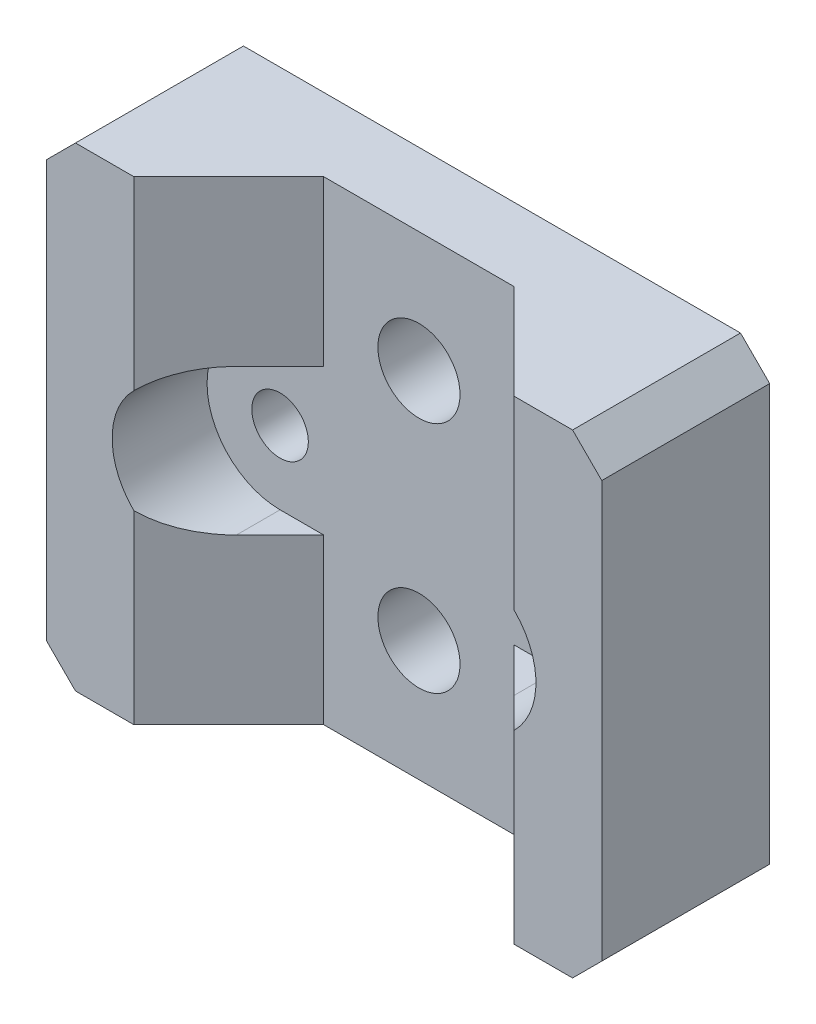
SolidWorks part; units mm, degrees
material "PET"
ref_plane "Front Plane" through (0, 0, 0) normal (0, 0, 1) x (1, 0, 0)
ref_plane "Top Plane" through (0, 0, 0) normal (0, 1, 0) x (1, 0, 0)
ref_plane "Right Plane" through (0, 0, 0) normal (1, 0, 0) x (0, 0, -1)
sketch "Sketch1" plane through (0, 0, 0) normal (0, 0, 1) x (1, 0, 0)
  line L0 (-124.0045, -34.7475) -> (-124.0045, -14.4275) construction
  line L1 (-148.1589, -8.5361) -> (-148.1589, -40.6389) construction
  line L2 (-148.1589, -3.95) -> (-99.85, -3.95)
  line L3 (-148.1589, -3.95) -> (-148.1589, -45.225)
  line L4 (-148.1589, -45.225) -> (-99.85, -45.225)
  line L5 (-99.85, -3.95) -> (-99.85, -45.225)
  line L6 (-148.1589, -3.95) -> (-99.85, -45.225) construction
  line L7 (-148.1589, -45.225) -> (-99.85, -3.95) construction
  point P4 (-124.0045, -24.5875)
  dimension "D1" = 41.275
extrude "Boss-Extrude1" add sketch "Sketch1" along normal blind 6.35
hole_wizard "#8 Clearance Hole1" positions "Sketch4" profile "Sketch5" hole size "#8" standard "ANSI Inch" end condition through all
sketch "Sketch4" plane through (0, 0, 6.35) normal (0, 0, 1) x (1, 0, 0)
  circle A0 centre (-111.9272, -24.5875) radius 2.9972 construction
  circle A1 centre (-136.0817, -24.5875) radius 2.9972 construction
  point P0 (-111.9272, -24.5875)
  point P2 (-136.0817, -24.5875)
sketch "Sketch5" plane through (-111.9272, -24.5875, 6.35) normal (1, 0, 0) x (0, -1, 0)
  line L0 (0, 0) -> (0, 6.35)
  line L1 (0, 6.35) -> (2.4574, 6.35)
  line L2 (2.4574, 6.35) -> (2.4574, 0)
  line L5 (2.4574, 0) -> (0, 0)
  line L11 (0, -6.35) -> (0, 107.95) construction
  dimension "Thru Hole Dia." = 4.9149
  dimension "Thru Hole Depth" = 6.35
hole_wizard "1/4 Clearance Hole1" positions "Sketch6" profile "Sketch7" hole size "1/4" standard "ANSI Inch" end condition through all
sketch "Sketch6" plane through (0, 0, 6.35) normal (0, 0, 1) x (1, 0, 0)
  circle A0 centre (-124.0045, -34.7475) radius 3.5712 construction
  circle A1 centre (-124.0045, -14.4275) radius 3.5712 construction
  point P0 (-124.0045, -14.4275)
  point P2 (-124.0045, -34.7475)
sketch "Sketch7" plane through (-124.0045, -14.4275, 6.35) normal (1, 0, 0) x (0, -1, 0)
  line L0 (0, 0) -> (0, 6.35)
  line L1 (0, 6.35) -> (3.5712, 6.35)
  line L2 (3.5712, 6.35) -> (3.5712, 0)
  line L5 (3.5712, 0) -> (0, 0)
  line L11 (0, -6.35) -> (0, 107.95) construction
  dimension "Thru Hole Dia." = 7.1425
  dimension "Thru Hole Depth" = 6.35
sketch "Sketch9" plane through (0, 0, 6.35) normal (0, 0, 1) x (1, 0, 0)
  line L4 (-99.85, -45.225) -> (-99.85, -3.95)
  line L5 (-99.85, -3.95) -> (-148.1589, -3.95)
  line L6 (-148.1589, -3.95) -> (-148.1589, -45.225)
  line L7 (-148.1589, -45.225) -> (-99.85, -45.225)
  line L8 (-99.85, -45.225) -> (-99.85, -3.95)
  line L10 (-148.1589, -3.95) -> (-148.1589, -45.225)
  dimension "D1" = 0
extrude "Extrude-Thin1" add sketch "Sketch9" along normal blind 8.255 thin thin type one direction reverse wall 6.35
chamfer "Chamfer2" distance 9.525 angle 45 2 edges at (-106.2, -24.5875, 6.35) (-141.8089, -24.5875, 6.35)
sketch "Sketch10" plane through (0, 0, 6.35) normal (0, 0, 1) x (1, 0, 0)
  line L0 (-136.0817, -24.5875) -> (-111.9272, -24.5875) construction
  line L1 (-136.0817, -18.2375) -> (-111.9272, -18.2375)
  line L2 (-136.0817, -30.9375) -> (-111.9272, -30.9375)
  arc A2 (-136.0817, -18.2375) -> (-136.0817, -30.9375) centre (-136.0817, -24.5875) ccw
  arc A3 (-111.9272, -30.9375) -> (-111.9272, -18.2375) centre (-111.9272, -24.5875) ccw
  point P3 (-124.0045, -24.5875)
  dimension "D1" = 6.35
extrude "Cut-Extrude1" cut sketch "Sketch10" along normal through all
chamfer "Chamfer1" distance 2.54 angle 45 4 edges at (-99.85, -3.95, 7.3025) (-148.1589, -3.95, 7.3025) (-99.85, -45.225, 7.3025) (-148.1589, -45.225, 7.3025)
hole_wizard "Hole1" positions "Sketch11" profile "Sketch12" legacy
sketch "Sketch11" plane through (-148.1589, 0, 0) normal (-1, 0, 0) x (0, 0, 1)
  point P0 (7.4422, -26.4544)
  point P3 (7.4422, -17.0945)
sketch "Sketch12" plane through (-148.1589, -26.4544, 7.4422) normal (0, 1, 0) x (0, 0, 1)
  line L0 (0, 0) -> (0, 2.921)
  line L1 (0, 2.921) -> (1.4986, 2.921)
  line L2 (1.4986, 2.921) -> (1.6383, 0)
  line L3 (1.6383, 0) -> (0, 0)
  line L4 (0, 110) -> (0, -10) construction
  dimension "Minor Diameter" = 2.9972
  dimension "Depth" = 2.921
  dimension "Major Diameter" = 3.2766
hole_wizard "#2 Clearance Hole1" positions "Sketch13" profile "Sketch14" hole size "#2" standard "ANSI Inch"
sketch "Sketch13" plane through (-148.1589, 0, 0) normal (-1, 0, 0) x (0, 0, 1)
  point P0 (7.4422, -17.0945)
  point P3 (7.4422, -26.4544)
sketch "Sketch14" plane through (-148.1589, -17.0945, 7.4422) normal (0, 1, 0) x (0, 0, 1)
  line L0 (0, 0) -> (0, 3.175)
  line L1 (0, 3.175) -> (1.3525, 3.175)
  line L2 (1.3525, 3.175) -> (1.3525, 0)
  line L5 (1.3525, 0) -> (0, 0)
  line L10 (0, 3.175) -> (-1.3526, 3.175) construction
  line L11 (0, -6.35) -> (0, 107.95) construction
  dimension "Hole Dia." = 2.7051
  dimension "Hole Depth" = 3.175
  dimension "Drill Angle" = 180
chamfer "Chamfer3" distance 1.27 angle 45 2 edges at (-120.4332, -34.7475, 0) (-120.4332, -14.4275, 0)
